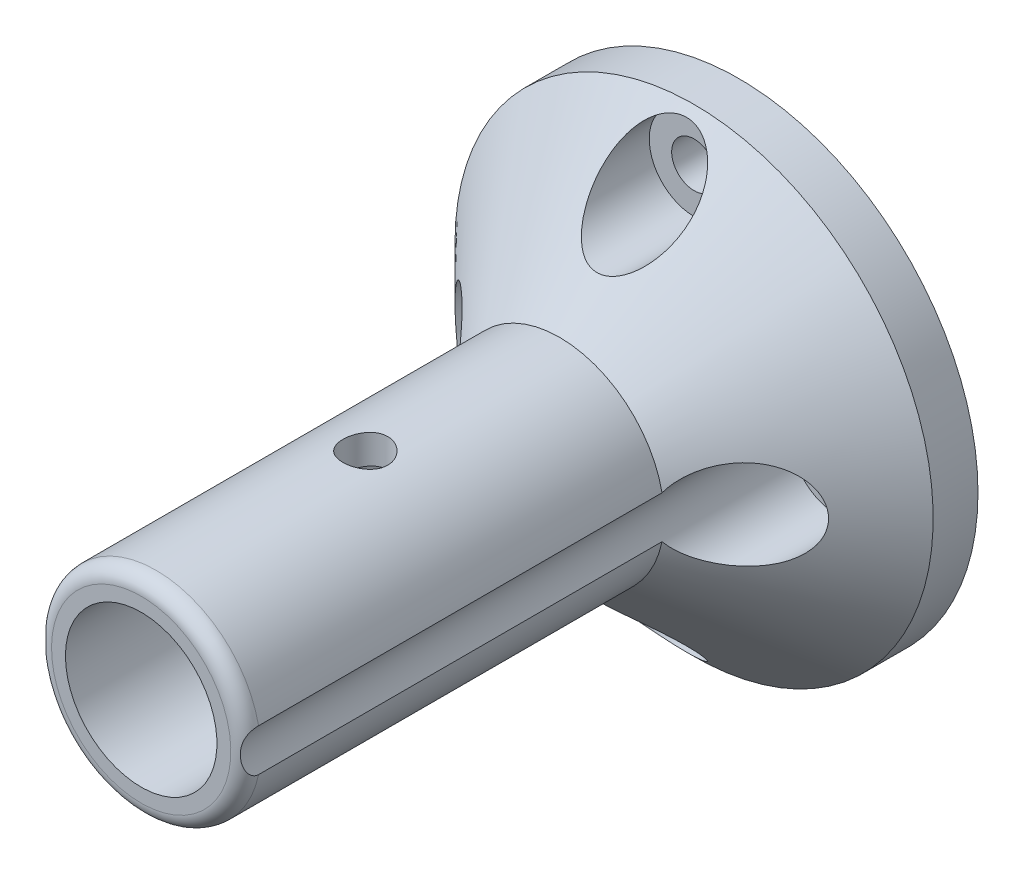
SolidWorks part; units mm, degrees
ref_plane "前视基准面" through (0, 0, 0) normal (0, 0, 1) x (1, 0, 0)
ref_plane "上视基准面" through (0, 0, 0) normal (0, 1, 0) x (1, 0, 0)
ref_plane "右视基准面" through (0, 0, 0) normal (1, 0, 0) x (0, 0, -1)
other "Configuration Table"
sketch "草图1" plane through (0, 0, 0) normal (0, 0, 1) x (1, 0, 0)
  circle A0 centre (0, 0) radius 16
  dimension "D1" = 32
extrude "凸台-拉伸1" add sketch "草图1" along normal blind 40
sketch "草图2" plane through (0, 0, 0) normal (0, 1, 0) x (1, 0, 0)
  line L0 (0, 0) -> (0, -20) construction
  line L1 (-16, -40) -> (-16, -3)
  line L2 (-16, 0) -> (-16, -40) construction
  line L3 (-16, -3) -> (-7, -12)
  line L4 (-7, -12) -> (-7, -40)
  line L5 (-16, -40) -> (16, -40) construction
  line L6 (-7, -40) -> (-16, -40)
  line L7 (16, 0) -> (-16, 0) construction
  line L8 (0, 0) -> (-5.07, 0)
  line L9 (0, 0) -> (0, -40)
  line L10 (0, -40) -> (-5.07, -40)
  line L11 (-5.07, 0) -> (-5.07, -40)
  dimension "D1" = 20
  dimension "D2" = 45
  dimension "D3" = 7
  dimension "D4" = 3
  dimension "D5" = 5.07
revolve "切除-旋转1" cut sketch "草图2" angle 360 about L0
sketch "草图3" plane through (0, 0, 0) normal (0, 0, 1) x (1, 0, 0)
  circle A0 centre (0, -12.5) radius 1.5 construction
  circle A1 centre (-9.5, 0) radius 1.5 construction
  circle A2 centre (9.5, 0) radius 1.5 construction
  circle A3 centre (0, 12.5) radius 1.5 construction
  circle A4 centre (0, -12.5) radius 1.5
  circle A5 centre (-9.5, 0) radius 1.5
  circle A6 centre (9.5, 0) radius 1.5
  circle A7 centre (0, 12.5) radius 1.5
extrude "切除-拉伸2" cut sketch "草图3" along normal through all
ref_plane "基准面1" through (0, 0, 3) normal (0, 0, 1) x (1, 0, 0)
sketch "草图4" plane through (0, 0, 3) normal (0, 0, 1) x (1, 0, 0)
  circle A0 centre (0, -12.5) radius 1.5 construction
  circle A1 centre (9.5, 0) radius 1.5 construction
  circle A2 centre (-9.5, 0) radius 1.5 construction
  circle A3 centre (0, 12.5) radius 1.5 construction
  circle A4 centre (0, -12.5) radius 1.5
  circle A5 centre (9.5, 0) radius 1.5
  circle A6 centre (-9.5, 0) radius 1.5
  circle A7 centre (0, 12.5) radius 1.5
  circle A8 centre (0, 12.5) radius 3
  circle A9 centre (-9.5, 0) radius 3
  circle A10 centre (9.5, 0) radius 3
  circle A11 centre (0, -12.5) radius 3
  dimension "D1" = 1.5
extrude "切除-拉伸3" cut sketch "草图4" along normal through all contours A5 | A6 | A7 | A4 | A9 | A10 | A8 | A11
sketch "草图5" plane through (0, 0, 0) normal (0, 1, 0) x (1, 0, 0)
  line L1 (-6.8553, -40) -> (6.8553, -40) construction
  circle A0 centre (0, -25) radius 1.5
  point P4 (0, -40)
  dimension "D2" = 3
  dimension "D1" = 15
extrude "切除-拉伸4" cut sketch "草图5" against normal through all and the other way through all
fillet "圆角1" radius 1 1 edges at (0, -7, 40)
